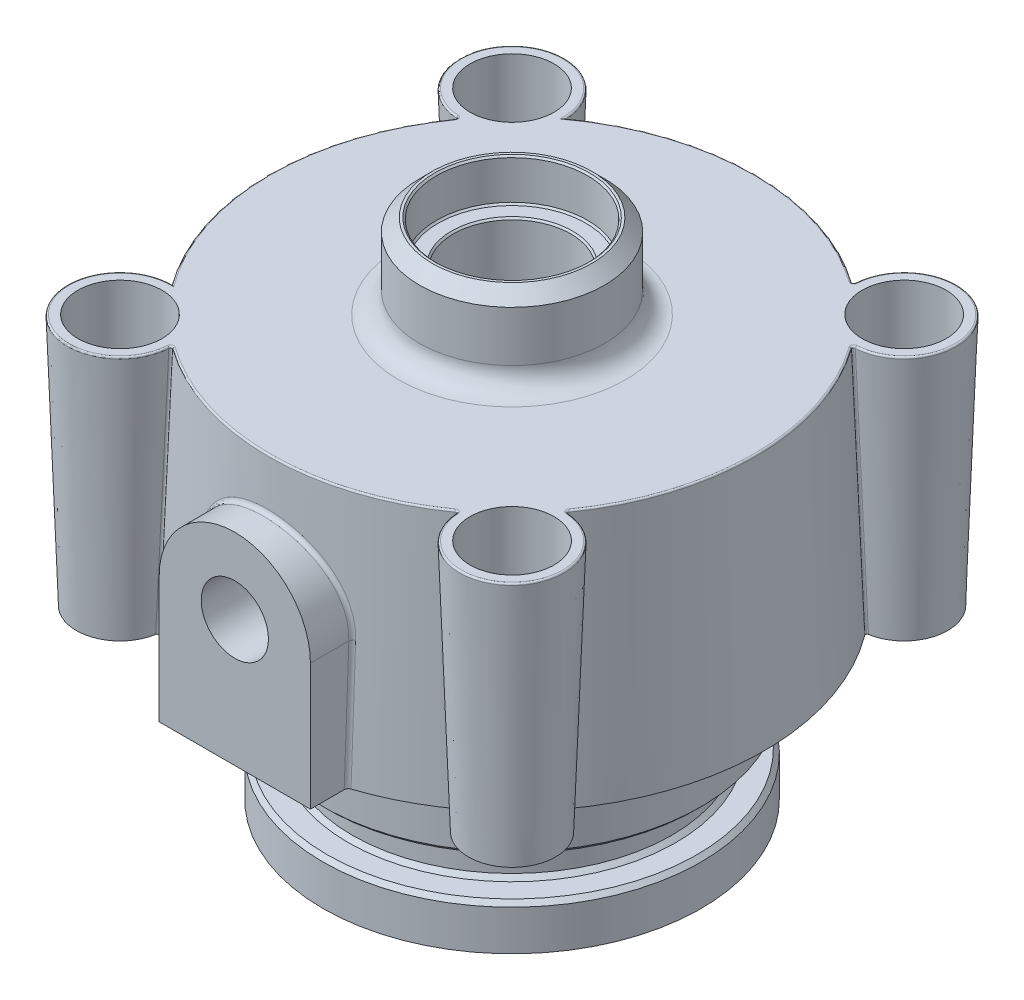
SolidWorks part; units mm, degrees
note: The reader was unsure of these and kept them because the rebuilt part matched: shared geometry of "Sketch8<4>", "Sketch8<5>", "Croquis17<2>".
material "Aleación 1060"
ref_plane "Front Plane" through (0, 0, 0) normal (0, 0, 1) x (1, 0, 0)
ref_plane "Top Plane" through (0, 0, 0) normal (0, 1, 0) x (1, 0, 0)
ref_plane "Right Plane" through (0, 0, 0) normal (1, 0, 0) x (0, 0, -1)
sketch "Sketch1" plane through (0, 0, 0) normal (0, 1, 0) x (1, 0, 0)
  circle A0 centre (0, 0) radius 22.5
  dimension "D1" = 45
extrude "Boss-Extrude1" add sketch "Sketch1" along normal blind 20
sketch "Sketch2" plane through (0, 20, 0) normal (0, 1, 0) x (1, 0, 0)
  circle A0 centre (0, 0) radius 30
  point P14 (0, 0)
  point P19 (0, 0)
  dimension "D1" = 60
extrude "Boss-Extrude2" add sketch "Sketch2" along normal blind 30 draft 2
sketch "Sketch3" plane through (0, 50, 0) normal (0, 1, 0) x (1, 0, 0)
  circle A0 centre (0, 0) radius 11
  dimension "D1" = 22
extrude "Boss-Extrude3" add sketch "Sketch3" along normal blind 10
ref_plane "Plane1" through (0, 0, 23) normal (0, 0, 1) x (1, 0, 0)
sketch "Sketch8" plane through (0, 0, 23) normal (0, 0, 1) x (1, 0, 0)
  line L0 (-9, 20) -> (-9, 35.0488)
  line L2 (9, 20) -> (9, 35.0488)
  line L3 (-22.5, 20) -> (22.5, 20) construction
  line L4 (-9, 20) -> (9, 20)
  line L6 (0, -55) -> (0, 55) construction
  line L7 (28.9524, 50) -> (-28.9524, 50) construction
  arc A0 (-9, 35.0488) -> (9, 35.0488) centre (0, 35.0488) cw
  circle A1 centre (0, 35.0488) radius 4
  dimension "D3" = 9
  dimension "D4" = 8
  dimension "D1" = 18
  dimension "D6" = 14.9512
sketch "Croquis1" plane through (0, 60, 0) normal (0, 1, 0) x (1, 0, 0)
  circle A0 centre (0, 0) radius 7
  dimension "D1" = 14
extrude "Cortar-Extruir1" cut sketch "Croquis1" against normal blind 90
sketch "Croquis2" plane through (0, 60, 0) normal (0, 1, 0) x (1, 0, 0)
  circle A0 centre (0, 0) radius 9
  dimension "D1" = 18
extrude "Cortar-Extruir2" cut sketch "Croquis2" against normal blind 5
sketch "Croquis3" plane through (0, 50, 0) normal (0, 1, 0) x (1, 0, 0)
  line L0 (0, 0) -> (-35.3676, 35.3676) construction
  line L1 (0, 0) -> (35.2874, -35.2874) construction
  line L2 (0, 0) -> (35.299, 35.299) construction
  line L3 (0, 0) -> (-35.4361, -35.4361) construction
  circle A9 centre (-23.3345, 23.3345) radius 6.235
  circle A12 centre (-23.3345, 23.3345) radius 5
  point P7 (-23.3345, 23.3345)
  point P9 (-21.2132, -21.2132)
  point P12 (21.2132, -21.2132)
  point P13 (-23.3345, 23.3345)
  point P14 (21.2132, 21.2132)
  circle M5 centre (0, 0) radius 28.9524
  dimension "D3" = 90
  dimension "D1" = 12.47
  dimension "D2" = 90
  dimension "D5" = 10
  dimension "D6" = 33
extrude "Saliente-Extruir1" add sketch "Croquis3" against normal blind 30 draft 2 contours A9 M5 | A9 A12 M5 | A12
pattern_circular "MatrizC1" count 4 over 360 about axis through (0, 0, 0) along (0, 1, 0) of "Saliente-Extruir1"
extrude "Saliente-Extruir2" add sketch "Sketch8" along normal blind 10
pattern_circular "MatrizC2" count 2 over 360 about axis through (0, 0, 0) along (0, 1, 0) of "Saliente-Extruir2"
sketch "Croquis10" plane through (0, 0, 23) normal (0, 0, 1) x (1, 0, 0)
  circle A0 centre (0, 35.0488) radius 3.9079
ref_plane "Plano1" through (0, 0, -37) normal (0, 0, -1) x (-1, 0, 0)
sketch "Croquis11" plane through (0, 0, -37) normal (0, 0, -1) x (-1, 0, 0)
  circle A0 centre (0, 35.0488) radius 4
extrude "Cortar-Extruir5" cut sketch "Croquis11" against normal blind 40
sketch "Croquis12" plane through (0, 0, 0) normal (1, 0, 0) x (0, 0, -1)
  line L0 (-22.5, 10) -> (-19, 10)
  line L1 (-22.5, 20) -> (-22.5, 0) construction
  line L2 (-19, 10) -> (-19, 5.3)
  line L3 (-19, 5.3) -> (-22.5, 5.3)
  line L4 (0, 0) -> (0, 60) construction
  line L5 (9, 60) -> (-9, 60) construction
  line L6 (-22.5, 10) -> (-22.5, 5.3)
  dimension "D1" = 4.7
  dimension "D2" = 3.5
revolve "Cortar-Revolución1" cut sketch "Croquis12" angle 360 about L4
sketch "Croquis13" plane through (0, 0, 0) normal (1, 0, 0) x (0, 0, -1)
  line L0 (0.0017, 13.7509) -> (-11.9983, 13.7509)
  line L1 (-11.9983, 13.7509) -> (-11.9983, 17.8541)
  line L2 (-11.9983, 17.8541) -> (0.0017, 17.8541)
  line L3 (0.0017, 17.8541) -> (0.0017, 13.7509)
  line L5 (0, 0) -> (0, 60) construction
  line L6 (9, 60) -> (-9, 60) construction
  line L7 (0.0017, 17.8541) -> (0.0017, 13.7509)
  dimension "D1" = 4.1033
  dimension "D2" = 12
revolve "Cortar-Revolución3" cut sketch "Croquis13" angle 360 about L3
extrude "Cortar-Extruir7" cut sketch "Sketch8<4>" along normal blind 7 contours A1
sketch "Sketch8<4>" plane through (0, 0, 23) normal (0, 0, 1) x (1, 0, 0) same geometry as "Sketch8"
extrude "Cortar-Extruir8" cut sketch "Sketch8<5>" against normal blind 0.2 contours A1
sketch "Sketch8<5>" plane through (0, 0, 23) normal (0, 0, 1) x (1, 0, 0) same geometry as "Sketch8"
sketch "Croquis16" plane through (0, 0, 0) normal (0, -1, 0) x (1, 0, 0)
  circle A0 centre (0, 14.3104) radius 3
  point P0 (0, 14.3104)
  dimension "D1" = 6
extrude "Cortar-Extruir9" cut sketch "Croquis16" against normal blind 34
ref_plane "Plano2" through (0, 0, 15) normal (0, 0, 1) x (1, 0, 0)
sketch "Croquis17" plane through (0, 0, 15) normal (0, 0, 1) x (1, 0, 0)
  circle A0 centre (0, 35.0488) radius 3.5
  dimension "D1" = 7
extrude "Cortar-Extruir10" cut sketch "Croquis17" along normal blind 8
cosmetic thread "Rosca cosmética10" parameters "D1"=5, "D2"=7.513
extrude "Cortar-Extruir11" cut sketch "Croquis17<2>" against normal blind 0.2
sketch "Croquis17<2>" plane through (0, 0, 15) normal (0, 0, 1) x (1, 0, 0) same geometry as "Croquis17"
ref_plane "Plano3" through (0, 0, 13) normal (0, 0, 1) x (1, 0, 0)
sketch "Croquis18" plane through (0, 0, 13) normal (0, 0, 1) x (1, 0, 0)
  circle A0 centre (0, 35.0488) radius 3
  dimension "D1" = 6
extrude "Cortar-Extruir12" cut sketch "Croquis18" along normal blind 8
sketch "Croquis19" plane through (0, 0, 0) normal (0, 0, 1) x (1, 0, 0)
  circle A0 centre (0, 35.0488) radius 2.5
  dimension "D1" = 5
extrude "Cortar-Extruir13" cut sketch "Croquis19" along normal blind 20
sketch "Croquis21" plane through (0, 50, 0) normal (0, 1, 0) x (1, 0, 0)
  circle A0 centre (-23.3345, 23.3345) radius 5
  circle A1 centre (-23.3345, 23.3345) radius 2.5
  point P0 (-23.3345, 23.3345)
  point P3 (25.8804, 25.8804)
  point P5 (28.4263, -23.3345)
  point P7 (-20.7886, -25.8804)
  point P10 (2.5459, 0)
  dimension "D2" = 10
  dimension "D1" = 4
extrude "Cortar-Extruir14" cut sketch "Croquis21" against normal blind 10 contours A1 | A0 A1
pattern_circular "MatrizC3" count 4 over 360 about axis through (0, 0, 0) along (0, 1, 0) of "Cortar-Extruir14"
fillet "Redondeo8" radius 0.2 14 edges at (-27.7433, 50, 27.7433) (-28.9524, 50, 0) (0, 50, 28.9524) (27.7433, 50, 27.7433) (-27.7433, 50, -27.7433) (28.9524, 50, 0) (-23.5243, 40.7577, -17.4253) (-17.4253, 40.7577, 23.5243) (23.5243, 40.7577, 17.4253) (17.9257, 26.8144, 23.7581) (17.4253, 40.7577, -23.5243) (23.7581, 26.8144, -17.9257) (0, 50, -28.9524) (27.7433, 50, -27.7433)
chamfer "Chaflán1" distance 0.25 angle 45 1 edges at (0, 38.0488, 14.8)
fillet "Redondeo10" radius 2.5 1 edges at (0, 50, 11)
sketch "Croquis24" plane through (0, 50, 0) normal (0, 1, 0) x (1, 0, 0)
  circle A0 centre (-23.3345, 23.3345) radius 3
  point P0 (-23.3345, 23.3345)
  dimension "D1" = 6
extrude "Cortar-Extruir16" cut sketch "Croquis24" against normal blind 30
sketch "Croquis25" plane through (0, 50, 0) normal (0, 1, 0) x (1, 0, 0)
  circle A1 centre (-23.3345, -23.3345) radius 3
  circle A2 centre (23.3345, -23.3345) radius 3
  circle A3 centre (23.3345, 23.3345) radius 3
  point P0 (23.3345, 23.3345)
  point P1 (-23.3345, -23.3345)
  point P3 (23.3345, -23.3345)
  dimension "D1" = 6
  dimension "D2" = 6
  dimension "D3" = 6
extrude "Cortar-Extruir17" cut sketch "Croquis25" against normal blind 30
chamfer "Chaflán2" distance 1.5 angle 45 1 edges at (0, 60, 11)
chamfer "Chaflán3" distance 0.5 angle 45 4 edges at (0, 10, -19) (0, 10, -22.5) (0, 5.3, -22.5) (0, 5.3, -19)
fillet "Redondeo11" radius 0.5 1 edges at (0, 20, 22.5)
chamfer "Chaflán4" distance 0.2 angle 45 2 edges at (0, 55, 7) (0, 55, 9)
chamfer "Chaflán5" distance 0.2 angle 45 4 edges at (0, 17.8541, -7) (0, 17.8541, -12.0017) (0, 13.7509, -12.0017) (0, 13.7509, 7)
chamfer "Chaflán6" distance 0.2 angle 45 1 edges at (0, 60, 9)
chamfer "Chaflán7" distance 0.5 angle 45 1 edges at (-4, 35.0488, -33)
cosmetic thread "Rosca cosmética11" parameters "D1"=15, "D2"=10
fillet "Redondeo13" radius 0.5 3 edges at (-0.7931, 44.0138, 29.1506)
fillet "Redondeo14" radius 0.5 3 edges at (0.7931, 44.0138, -29.1506)
